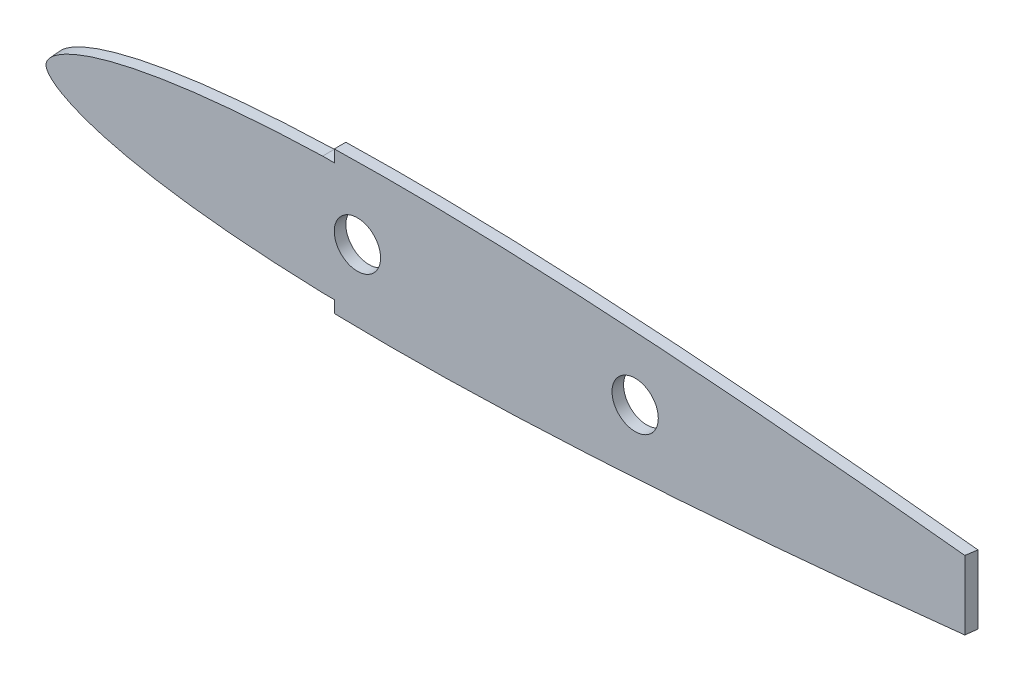
SolidWorks part; units mm, degrees
material "Balsa"
ref_plane "Front Plane" through (0, 0, 0) normal (0, 0, 1) x (1, 0, 0)
ref_plane "Top Plane" through (0, 0, 0) normal (0, 1, 0) x (1, 0, 0)
ref_plane "Right Plane" through (0, 0, 0) normal (1, 0, 0) x (0, 0, -1)
curve "Curve1"
  spline degree 3 poles (329.1277, -0.5559, 0) (329.1277, 0.5559, 0) (328.019, 0.4202, 0) (326.6142, 0.8156, 0) (324.0379, 1.0601, 0) (320.5673, 1.5846, 0) (316.0966, 2.17, 0) (310.7052, 2.8915, 0) (304.4072, 3.7071, 0) (297.2481, 4.6151, 0) (289.2699, 5.5996, 0) (280.5223, 6.6474, 0) (271.0592, 7.7455, 0) (260.9388, 8.8788, 0) (250.2237, 10.0335, 0) (238.9798, 11.1954, 0) (227.2766, 12.3494, 0) (215.1861, 13.4792, 0) (202.7829, 14.5702, 0) (190.1436, 15.604, 0) (177.3458, 16.5638, 0) (164.4685, 17.4317, 0) (151.5911, 18.1897, 0) (138.7929, 18.8185, 0) (126.1528, 19.3014, 0) (113.7486, 19.6226, 0) (101.6567, 19.7665, 0) (89.9516, 19.7217, 0) (78.7054, 19.4794, 0) (67.9873, 19.0335, 0) (57.8633, 18.3829, 0) (48.3955, 17.5295, 0) (39.6421, 16.48, 0) (31.6562, 15.2433, 0) (24.4863, 13.8323, 0) (18.1744, 12.263, 0) (12.7564, 10.5507, 0) (8.2599, 8.7113, 0) (4.699, 6.7573, 0) (2.0794, 4.6848, 0) (0.4016, 2.4437, 0) (-0.1872, 0, 0) (0.4016, -2.4437, 0) (2.0794, -4.6848, 0) (4.699, -6.7573, 0) (8.2599, -8.7113, 0) (12.7564, -10.5507, 0) (18.1744, -12.263, 0) (24.4863, -13.8323, 0) (31.6562, -15.2433, 0) (39.6421, -16.48, 0) (48.3955, -17.5295, 0) (57.8633, -18.3829, 0) (67.9873, -19.0335, 0) (78.7054, -19.4794, 0) (89.9516, -19.7217, 0) (101.6567, -19.7665, 0) (113.7486, -19.6226, 0) (126.1528, -19.3014, 0) (138.7929, -18.8185, 0) (151.5911, -18.1897, 0) (164.4685, -17.4317, 0) (177.3458, -16.5638, 0) (190.1436, -15.604, 0) (202.7829, -14.5702, 0) (215.1861, -13.4792, 0) (227.2766, -12.3494, 0) (238.9798, -11.1954, 0) (250.2237, -10.0335, 0) (260.9388, -8.8788, 0) (271.0592, -7.7455, 0) (280.5223, -6.6474, 0) (289.2699, -5.5996, 0) (297.2481, -4.6151, 0) (304.4072, -3.7071, 0) (310.7052, -2.8915, 0) (316.0966, -2.17, 0) (320.5673, -1.5846, 0) (324.0379, -1.0601, 0) (326.6142, -0.8156, 0) (328.019, -0.4202, 0) (329.1277, -0.5559, 0) (329.1277, 0.5559, 0) (328.019, 0.4202, 0) knots -0.004279 -0.001997 -0.001234 0 0.000762 0.003045 0.006832 0.012101 0.018818 0.026939 0.036415 0.047185 0.05918 0.072328 0.086544 0.101741 0.117823 0.134691 0.15224 0.170361 0.188941 0.207865 0.227016 0.246276 0.265525 0.284645 0.30352 0.322035 0.340078 0.357543 0.374325 0.39033 0.405464 0.419644 0.432793 0.444844 0.455738 0.465429 0.473886 0.481102 0.487102 0.491975 0.495931 0.499383 0.502835 0.50679 0.511664 0.517664 0.524879 0.533337 0.543028 0.553922 0.565972 0.579122 0.593302 0.608436 0.62444 0.641223 0.658687 0.676731 0.695245 0.714121 0.733241 0.75249 0.77175 0.7909 0.809825 0.828404 0.846525 0.864074 0.880942 0.897025 0.912222 0.926438 0.939585 0.951581 0.962351 0.971826 0.979948 0.986664 0.991933 0.995721 0.998003 0.998766 1 1.000762 1.003045 1.006832 periodic
sketch "Sketch1" plane through (0, 0, 0) normal (0, 0, 1) x (1, 0, 0)
  spline S0 degree 3 poles (329.1277, -0.5559) (329.1277, 0.5559) (328.019, 0.4202) (326.6142, 0.8156) (324.0379, 1.0601) (320.5673, 1.5846) (316.0966, 2.17) (310.7052, 2.8915) (304.4072, 3.7071) (297.2481, 4.6151) (289.2699, 5.5996) (280.5223, 6.6474) (271.0592, 7.7455) (260.9388, 8.8788) (250.2237, 10.0335) (238.9798, 11.1954) (227.2766, 12.3494) (215.1861, 13.4792) (202.7829, 14.5702) (190.1436, 15.604) (177.3458, 16.5638) (164.4685, 17.4317) (151.5911, 18.1897) (138.7929, 18.8185) (126.1528, 19.3014) (113.7486, 19.6226) (101.6567, 19.7665) (89.9516, 19.7217) (78.7054, 19.4794) (67.9873, 19.0335) (57.8633, 18.3829) (48.3955, 17.5295) (39.6421, 16.48) (31.6562, 15.2433) (24.4863, 13.8323) (18.1744, 12.263) (12.7564, 10.5507) (8.2599, 8.7113) (4.699, 6.7573) (2.0794, 4.6848) (0.4016, 2.4437) (-0.1872, 0) (0.4016, -2.4437) (2.0794, -4.6848) (4.699, -6.7573) (8.2599, -8.7113) (12.7564, -10.5507) (18.1744, -12.263) (24.4863, -13.8323) (31.6562, -15.2433) (39.6421, -16.48) (48.3955, -17.5295) (57.8633, -18.3829) (67.9873, -19.0335) (78.7054, -19.4794) (89.9516, -19.7217) (101.6567, -19.7665) (113.7486, -19.6226) (126.1528, -19.3014) (138.7929, -18.8185) (151.5911, -18.1897) (164.4685, -17.4317) (177.3458, -16.5638) (190.1436, -15.604) (202.7829, -14.5702) (215.1861, -13.4792) (227.2766, -12.3494) (238.9798, -11.1954) (250.2237, -10.0335) (260.9388, -8.8788) (271.0592, -7.7455) (280.5223, -6.6474) (289.2699, -5.5996) (297.2481, -4.6151) (304.4072, -3.7071) (310.7052, -2.8915) (316.0966, -2.17) (320.5673, -1.5846) (324.0379, -1.0601) (326.6142, -0.8156) (328.019, -0.4202) (329.1277, -0.5559) (329.1277, 0.5559) (328.019, 0.4202) knots -0.004279 -0.001997 -0.001234 0 0.000762 0.003045 0.006832 0.012101 0.018818 0.026939 0.036415 0.047185 0.05918 0.072328 0.086544 0.101741 0.117823 0.134691 0.15224 0.170361 0.188941 0.207865 0.227016 0.246276 0.265525 0.284645 0.30352 0.322035 0.340078 0.357543 0.374325 0.39033 0.405464 0.419644 0.432793 0.444844 0.455738 0.465429 0.473886 0.481102 0.487102 0.491975 0.495931 0.499383 0.502835 0.50679 0.511664 0.517664 0.524879 0.533337 0.543028 0.553922 0.565972 0.579122 0.593302 0.608436 0.62444 0.641223 0.658687 0.676731 0.695245 0.714121 0.733241 0.75249 0.77175 0.7909 0.809825 0.828404 0.846525 0.864074 0.880942 0.897025 0.912222 0.926438 0.939585 0.951581 0.962351 0.971826 0.979948 0.986664 0.991933 0.995721 0.998003 0.998766 1 1.000762 1.003045 1.006832 only from (328.93, 0.4145) to (328.93, 0.4145) construction
  spline S1 degree 3 poles (329.1277, -0.5559) (329.1277, 0.5559) (328.019, 0.4202) (326.6142, 0.8156) (324.0379, 1.0601) (320.5673, 1.5846) (316.0966, 2.17) (310.7052, 2.8915) (304.4072, 3.7071) (297.2481, 4.6151) (289.2699, 5.5996) (280.5223, 6.6474) (271.0592, 7.7455) (260.9388, 8.8788) (250.2237, 10.0335) (238.9798, 11.1954) (227.2766, 12.3494) (215.1861, 13.4792) (202.7829, 14.5702) (190.1436, 15.604) (177.3458, 16.5638) (164.4685, 17.4317) (151.5911, 18.1897) (138.7929, 18.8185) (126.1528, 19.3014) (113.7486, 19.6226) (101.6567, 19.7665) (89.9516, 19.7217) (78.7054, 19.4794) (67.9873, 19.0335) (57.8633, 18.3829) (48.3955, 17.5295) (39.6421, 16.48) (31.6562, 15.2433) (24.4863, 13.8323) (18.1744, 12.263) (12.7564, 10.5507) (8.2599, 8.7113) (4.699, 6.7573) (2.0794, 4.6848) (0.4016, 2.4437) (-0.1872, 0) (0.4016, -2.4437) (2.0794, -4.6848) (4.699, -6.7573) (8.2599, -8.7113) (12.7564, -10.5507) (18.1744, -12.263) (24.4863, -13.8323) (31.6562, -15.2433) (39.6421, -16.48) (48.3955, -17.5295) (57.8633, -18.3829) (67.9873, -19.0335) (78.7054, -19.4794) (89.9516, -19.7217) (101.6567, -19.7665) (113.7486, -19.6226) (126.1528, -19.3014) (138.7929, -18.8185) (151.5911, -18.1897) (164.4685, -17.4317) (177.3458, -16.5638) (190.1436, -15.604) (202.7829, -14.5702) (215.1861, -13.4792) (227.2766, -12.3494) (238.9798, -11.1954) (250.2237, -10.0335) (260.9388, -8.8788) (271.0592, -7.7455) (280.5223, -6.6474) (289.2699, -5.5996) (297.2481, -4.6151) (304.4072, -3.7071) (310.7052, -2.8915) (316.0966, -2.17) (320.5673, -1.5846) (324.0379, -1.0601) (326.6142, -0.8156) (328.019, -0.4202) (329.1277, -0.5559) (329.1277, 0.5559) (328.019, 0.4202) knots -0.004279 -0.001997 -0.001234 0 0.000762 0.003045 0.006832 0.012101 0.018818 0.026939 0.036415 0.047185 0.05918 0.072328 0.086544 0.101741 0.117823 0.134691 0.15224 0.170361 0.188941 0.207865 0.227016 0.246276 0.265525 0.284645 0.30352 0.322035 0.340078 0.357543 0.374325 0.39033 0.405464 0.419644 0.432793 0.444844 0.455738 0.465429 0.473886 0.481102 0.487102 0.491975 0.495931 0.499383 0.502835 0.50679 0.511664 0.517664 0.524879 0.533337 0.543028 0.553922 0.565972 0.579122 0.593302 0.608436 0.62444 0.641223 0.658687 0.676731 0.695245 0.714121 0.733241 0.75249 0.77175 0.7909 0.809825 0.828404 0.846525 0.864074 0.880942 0.897025 0.912222 0.926438 0.939585 0.951581 0.962351 0.971826 0.979948 0.986664 0.991933 0.995721 0.998003 0.998766 1 1.000762 1.003045 1.006832 only from (328.93, 0.4145) to (328.93, 0.4145)
extrude "Boss-Extrude1" add sketch "Sketch1" along normal blind 3.175
sketch "Sketch2" plane through (0, 0, 3.175) normal (0, 0, 1) x (1, 0, 0)
  circle A0 centre (88.9, 0) radius 6.35
  circle A1 centre (165.1, 0) radius 6.35
  dimension "D1" = 12.7
  dimension "D2" = 12.7
  dimension "D3" = 0
  dimension "D4" = 0
  dimension "D5" = 88.9
  dimension "D6" = 165.1
extrude "Cut-Extrude1" cut sketch "Sketch2" against normal through all
sketch "Sketch3" plane through (0, 0, 0) normal (0, 1, 0) x (1, 0, 0)
  line L2 (255.9922, 0) -> (255.5456, -3.175)
  line L4 (0, 0) -> (329.0783, 0) construction
  line L5 (255.9922, 0) -> (329.0783, 0)
  line L6 (0, -3.175) -> (329.0783, -3.175) construction
  line L7 (255.5456, -3.175) -> (329.0783, -3.175)
  line L8 (329.0783, -3.175) -> (329.0783, 0) construction
  line L9 (329.0783, -3.175) -> (329.0783, 0)
extrude "Cut-Extrude2" cut sketch "Sketch3" against normal through all both and the other way through all
sketch "Sketch4" plane through (0, 0, 3.175) normal (0, 0, 1) x (1, 0, 0)
  line L0 (82.55, -19.5157) -> (82.55, -16.251)
  line L1 (82.55, -19.5157) -> (82.55, -16.251)
  line L2 (82.55, 16.251) -> (82.55, 19.5157)
  line L3 (82.55, 16.251) -> (82.55, 19.5157)
  line L4 (79.375, 16.251) -> (82.55, 16.251)
  line L5 (79.375, 16.251) -> (82.55, 16.251)
  line L6 (82.55, -16.251) -> (79.375, -16.251)
  line L7 (82.55, -16.251) -> (79.375, -16.251)
  line L9 (0.5415, 30.0212) -> (-2.1465, -32.8507)
  line L11 (82.55, -19.5157) -> (82.55, -25.5256)
  line L12 (82.55, -25.5256) -> (-2.1465, -32.8507)
  line L13 (82.55, 19.5157) -> (82.55, 26.8567)
  line L14 (82.55, 26.8567) -> (0.5415, 30.0212)
  spline S0 degree 3 poles (633.1488, 1884.3857) (572.2625, -178.71) (305.5166, 33.3533) (56.3074, 15.0016) (53.0215, 14.7179) (46.4592, 14.0473) (43.1826, 13.6609) (38.2769, 12.9805) (36.6432, 12.7368) (33.3795, 12.2092) (31.7481, 11.9252) (28.4987, 11.3107) (26.8806, 10.9799) (23.6603, 10.2608) (22.0581, 9.8726) (18.8752, 9.0193) (17.294, 8.5555) (14.1628, 7.5173) (12.612, 6.9461) (10.325, 5.9501) (9.5678, 5.594) (8.4619, 5.0175) (8.0979, 4.8178) (7.3817, 4.3992) (7.0294, 4.1804) (6.3393, 3.7196) (6.0012, 3.478) (5.3468, 2.9597) (5.0286, 2.6811) (4.4393, 2.0844) (4.1647, 1.7684) (3.8202, 1.2362) (3.7187, 1.0506) (3.6, 0.7593) (3.5654, 0.6591) (3.5092, 0.4554) (3.4875, 0.3518) (3.4597, 0.1436) (3.4536, 0.0389) (3.4614, -0.1718) (3.475, -0.2784) (3.5362, -0.5884) (3.6037, -0.7864) (3.7802, -1.1687) (3.8895, -1.352) (4.1294, -1.699) (4.2613, -1.865) (4.6778, -2.343) (4.9796, -2.6343) (5.6143, -3.1819) (5.9478, -3.4375) (6.9802, -4.1679) (7.6955, -4.5988) (9.1563, -5.3913) (9.9024, -5.7532) (11.4148, -6.4327) (12.1816, -6.7494) (13.7316, -7.3466) (14.5148, -7.6272) (16.0932, -8.162) (16.8886, -8.4152) (18.4829, -8.8963) (19.2828, -9.1247) (21.6889, -9.78) (23.302, -10.1762) (26.5415, -10.9085) (28.1678, -11.2447) (33.063, -12.1804) (36.3505, -12.7096) (42.9384, -13.6309) (46.2381, -14.0227) (52.8462, -14.7022) (56.1547, -14.9893) (304.7791, -33.3808) (568.8134, 178.1804) (647.8146, -1880.4778) knots -4.547287 -4.547287 -4.547287 -4.547287 0.125 0.125 0.1875 0.1875 0.25 0.25 0.28125 0.28125 0.3125 0.3125 0.34375 0.34375 0.375 0.375 0.40625 0.40625 0.4375 0.4375 0.453125 0.453125 0.460938 0.460938 0.46875 0.46875 0.476563 0.476563 0.484375 0.484375 0.492188 0.492188 0.496094 0.496094 0.498047 0.498047 0.5 0.5 0.501953 0.501953 0.503906 0.503906 0.507813 0.507813 0.511719 0.511719 0.515625 0.515625 0.523438 0.523438 0.53125 0.53125 0.546875 0.546875 0.5625 0.5625 0.578125 0.578125 0.59375 0.59375 0.609375 0.609375 0.625 0.625 0.65625 0.65625 0.6875 0.6875 0.75 0.75 0.8125 0.8125 0.875 0.875 5.504372 5.504372 5.504372 5.504372 only from (79.375, 16.251) to (79.375, -16.251)
  spline S1 degree 3 poles (79.375, 16.251) (72.7703, 16.048) (66.1762, 15.7283) (56.3074, 15.0016) (53.0215, 14.7179) (46.4592, 14.0473) (43.1826, 13.6609) (38.2769, 12.9805) (36.6432, 12.7368) (33.3795, 12.2092) (31.7481, 11.9252) (28.4987, 11.3107) (26.8806, 10.9799) (23.6603, 10.2608) (22.0581, 9.8726) (18.8752, 9.0193) (17.294, 8.5555) (14.1628, 7.5173) (12.612, 6.9461) (10.325, 5.9501) (9.5678, 5.594) (8.4619, 5.0175) (8.0979, 4.8178) (7.3817, 4.3992) (7.0294, 4.1804) (6.3393, 3.7196) (6.0012, 3.478) (5.3468, 2.9597) (5.0286, 2.6811) (4.4393, 2.0844) (4.1647, 1.7684) (3.8202, 1.2362) (3.7187, 1.0506) (3.6, 0.7593) (3.5654, 0.6591) (3.5092, 0.4554) (3.4875, 0.3518) (3.4597, 0.1436) (3.4536, 0.0389) (3.4614, -0.1718) (3.475, -0.2784) (3.5362, -0.5884) (3.6037, -0.7864) (3.7802, -1.1687) (3.8895, -1.352) (4.1294, -1.699) (4.2613, -1.865) (4.6778, -2.343) (4.9796, -2.6343) (5.6143, -3.1819) (5.9478, -3.4375) (6.9802, -4.1679) (7.6955, -4.5988) (9.1563, -5.3913) (9.9024, -5.7532) (11.4148, -6.4327) (12.1816, -6.7494) (13.7316, -7.3466) (14.5148, -7.6272) (16.0932, -8.162) (16.8886, -8.4152) (18.4829, -8.8963) (19.2828, -9.1247) (21.6889, -9.78) (23.302, -10.1762) (26.5415, -10.9085) (28.1678, -11.2447) (33.063, -12.1804) (36.3505, -12.7096) (42.9384, -13.6309) (46.2381, -14.0227) (52.8462, -14.7022) (56.1547, -14.9893) (66.0905, -15.7243) (72.7279, -16.0468) (79.375, -16.251) knots 0 0 0 0 0.125 0.125 0.1875 0.1875 0.25 0.25 0.28125 0.28125 0.3125 0.3125 0.34375 0.34375 0.375 0.375 0.40625 0.40625 0.4375 0.4375 0.453125 0.453125 0.460938 0.460938 0.46875 0.46875 0.476563 0.476563 0.484375 0.484375 0.492188 0.492188 0.496094 0.496094 0.498047 0.498047 0.5 0.5 0.501953 0.501953 0.503906 0.503906 0.507813 0.507813 0.511719 0.511719 0.515625 0.515625 0.523438 0.523438 0.53125 0.53125 0.546875 0.546875 0.5625 0.5625 0.578125 0.578125 0.59375 0.59375 0.609375 0.609375 0.625 0.625 0.65625 0.65625 0.6875 0.6875 0.75 0.75 0.8125 0.8125 0.875 0.875 1 1 1 1
sketch "Sketch5" plane through (0, 0, 0) normal (0, 0, -1) x (-1, 0, 0)
  line L0 (-82.55, 16.2869) -> (-82.55, 19.5505)
  line L1 (-82.55, 16.2869) -> (-82.55, 19.5505)
  line L2 (-82.55, -16.2869) -> (-79.375, -16.2868)
  line L3 (-82.55, -16.2869) -> (-79.375, -16.2868)
  line L4 (-82.55, -19.5505) -> (-82.55, -16.2869)
  line L5 (-82.55, -19.5505) -> (-82.55, -16.2869)
  line L6 (-79.375, 16.2868) -> (-82.55, 16.2869)
  line L7 (-79.375, 16.2868) -> (-82.55, 16.2869)
  line L9 (6.7812, 29.8614) -> (6.7812, -36.6391)
  line L11 (-82.55, -19.5505) -> (-82.55, -25.5256)
  line L12 (-82.55, -25.5256) -> (6.7812, -36.6391)
  line L13 (-82.55, 19.5505) -> (-82.55, 31.3589)
  line L15 (6.7812, 29.8614) -> (-82.55, 31.3589)
  spline S0 degree 3 poles (-649.3041, -1879.8024) (-570.0365, 178.4573) (-305.3204, -33.3955) (-56.0669, -15.0268) (-52.7459, -14.7395) (-46.1126, -14.0593) (-42.8003, -13.6669) (-36.1868, -12.7438) (-32.8863, -12.2135) (-27.9721, -11.2755) (-26.3395, -10.9383) (-23.0875, -10.204) (-21.4682, -9.8067) (-19.0528, -9.1496) (-18.2498, -8.9205) (-16.6494, -8.4378) (-15.851, -8.1838) (-13.4745, -7.3791) (-11.9142, -6.7899) (-9.6372, -5.7671) (-8.8884, -5.4038) (-7.4222, -4.6083) (-6.7042, -4.1757) (-5.6681, -3.4422) (-5.3336, -3.1854) (-4.697, -2.6353) (-4.3942, -2.3426) (-3.9768, -1.8622) (-3.8446, -1.6954) (-3.6045, -1.3465) (-3.4952, -1.1622) (-3.3192, -0.7778) (-3.2523, -0.5788) (-3.1923, -0.2672) (-3.1792, -0.16) (-3.1725, 0.0517) (-3.1793, 0.1568) (-3.2233, 0.4702) (-3.2839, 0.6772) (-3.4449, 1.0664) (-3.5476, 1.2523) (-3.8954, 1.7853) (-4.1717, 2.1017) (-4.7642, 2.6996) (-5.084, 2.9787) (-5.7415, 3.4979) (-6.081, 3.74) (-7.1204, 4.4324) (-7.842, 4.8477) (-9.3223, 5.618) (-10.0826, 5.9749) (-12.3785, 6.9731) (-13.9351, 7.5453) (-17.0774, 8.5855) (-18.6641, 9.05) (-21.8582, 9.9049) (-23.466, 10.2937) (-26.6977, 11.014) (-28.3216, 11.3453) (-31.5826, 11.9608) (-33.2197, 12.2452) (-36.4949, 12.7735) (-38.1343, 13.0174) (-43.0571, 13.6986) (-46.345, 14.0853) (-52.9302, 14.7561) (-56.2275, 15.0397) (-306.0585, 33.3625) (-573.4075, -178.961) (-635.2065, 1883.5473) knots -4.498533 -4.498533 -4.498533 -4.498533 0.125 0.125 0.1875 0.1875 0.25 0.25 0.3125 0.3125 0.34375 0.34375 0.375 0.375 0.390625 0.390625 0.40625 0.40625 0.4375 0.4375 0.453125 0.453125 0.46875 0.46875 0.476563 0.476563 0.484375 0.484375 0.488281 0.488281 0.492188 0.492188 0.496094 0.496094 0.498047 0.498047 0.5 0.5 0.503906 0.503906 0.507813 0.507813 0.515625 0.515625 0.523438 0.523438 0.53125 0.53125 0.546875 0.546875 0.5625 0.5625 0.59375 0.59375 0.625 0.625 0.65625 0.65625 0.6875 0.6875 0.71875 0.71875 0.75 0.75 0.8125 0.8125 0.875 0.875 5.542695 5.542695 5.542695 5.542695 only from (-79.375, -16.2868) to (-79.375, 16.2868)
  spline S1 degree 3 poles (-79.375, -16.2868) (-72.7027, -16.0836) (-66.0402, -15.7617) (-56.0669, -15.0268) (-52.7459, -14.7395) (-46.1126, -14.0593) (-42.8003, -13.6669) (-36.1868, -12.7438) (-32.8863, -12.2135) (-27.9721, -11.2755) (-26.3395, -10.9383) (-23.0875, -10.204) (-21.4682, -9.8067) (-19.0528, -9.1496) (-18.2498, -8.9205) (-16.6494, -8.4378) (-15.851, -8.1838) (-13.4745, -7.3791) (-11.9142, -6.7899) (-9.6372, -5.7671) (-8.8884, -5.4038) (-7.4222, -4.6083) (-6.7042, -4.1757) (-5.6681, -3.4422) (-5.3336, -3.1854) (-4.697, -2.6353) (-4.3942, -2.3426) (-3.9768, -1.8622) (-3.8446, -1.6954) (-3.6045, -1.3465) (-3.4952, -1.1622) (-3.3192, -0.7778) (-3.2523, -0.5788) (-3.1923, -0.2672) (-3.1792, -0.16) (-3.1725, 0.0517) (-3.1793, 0.1568) (-3.2233, 0.4702) (-3.2839, 0.6772) (-3.4449, 1.0664) (-3.5476, 1.2523) (-3.8954, 1.7853) (-4.1717, 2.1017) (-4.7642, 2.6996) (-5.084, 2.9787) (-5.7415, 3.4979) (-6.081, 3.74) (-7.1204, 4.4324) (-7.842, 4.8477) (-9.3223, 5.618) (-10.0826, 5.9749) (-12.3785, 6.9731) (-13.9351, 7.5453) (-17.0774, 8.5855) (-18.6641, 9.05) (-21.8582, 9.9049) (-23.466, 10.2937) (-26.6977, 11.014) (-28.3216, 11.3453) (-31.5826, 11.9608) (-33.2197, 12.2452) (-36.4949, 12.7735) (-38.1343, 13.0174) (-43.0571, 13.6986) (-46.345, 14.0853) (-52.9302, 14.7561) (-56.2275, 15.0397) (-66.1305, 15.766) (-72.7475, 16.085) (-79.375, 16.2868) knots 0 0 0 0 0.125 0.125 0.1875 0.1875 0.25 0.25 0.3125 0.3125 0.34375 0.34375 0.375 0.375 0.390625 0.390625 0.40625 0.40625 0.4375 0.4375 0.453125 0.453125 0.46875 0.46875 0.476563 0.476563 0.484375 0.484375 0.488281 0.488281 0.492188 0.492188 0.496094 0.496094 0.498047 0.498047 0.5 0.5 0.503906 0.503906 0.507813 0.507813 0.515625 0.515625 0.523438 0.523438 0.53125 0.53125 0.546875 0.546875 0.5625 0.5625 0.59375 0.59375 0.625 0.625 0.65625 0.65625 0.6875 0.6875 0.71875 0.71875 0.75 0.75 0.8125 0.8125 0.875 0.875 1 1 1 1
loft "Cut-Loft1" cut profiles "Sketch4", "Sketch5" connector at (0.5415, 30.0212, 3.175) connector at (-6.7812, 29.8614, 0)
